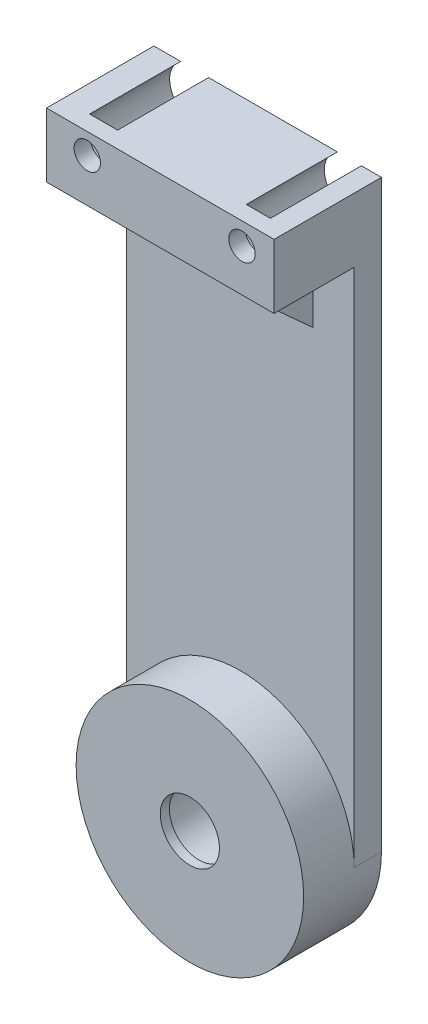
SolidWorks part; units mm, degrees
ref_plane "Plano frontal" through (0, 0, 0) normal (0, 0, 1) x (1, 0, 0)
ref_plane "Plano superior" through (0, 0, 0) normal (0, 1, 0) x (1, 0, 0)
ref_plane "Plano direito" through (0, 0, 0) normal (1, 0, 0) x (0, 0, -1)
sketch "Esboço2" plane through (0, 0, 0) normal (0, 0, 1) x (1, 0, 0)
  circle A0 centre (-0.4749, -0.0634) radius 12.5
  arc A1 (12.0247, -0.1594) -> (-12.9746, 0.0325) centre (-0.4749, -0.0634) ccw construction
extrude "Ressalto-extrusão1" add sketch "Esboço2" against normal offset from surface (5.55 mm away) 2 offset beyond the face yes
sketch "Esboço4" plane through (0, 0, -5.55) normal (0, 0, -1) x (-1, 0, 0)
  line L0 (-12.0251, -0.0634) -> (-12.0251, 64.1202)
  line L1 (12.9749, -0.0634) -> (12.9749, 64.1202)
  line L2 (12.9749, 64.1202) -> (-12.0251, 64.1202)
  arc A0 (-12.0251, -0.0634) -> (12.9749, -0.0634) centre (0.4749, -0.0634) ccw
  circle A4 centre (0.4749, -0.0634) radius 12.5 construction
  dimension "D1" = 0.5
extrude "Ressalto-extrusão3" add sketch "Esboço4" along normal blind 3
sketch "Esboço5" plane through (0, 0, -8.55) normal (0, 0, -1) x (-1, 0, 0)
  line L0 (12.9749, -0.0634) -> (12.9749, 64.1202) construction
  line L1 (-12.0251, 64.1202) -> (12.9749, 64.1202)
  line L2 (-12.0251, 64.1202) -> (-12.0251, 57.0691)
  line L3 (-12.0251, 57.0691) -> (12.9749, 57.0691)
  line L5 (12.9749, 57.0691) -> (12.9749, 64.1202)
extrude "Ressalto-extrusão4" add sketch "Esboço5" against normal up to surface (11.8 mm away)
hole_wizard "Rebaixo para SHCS M2.51" positions "Esboço6" profile "Esboço7" counterbore size "M2.5" standard "Ansi Metric" end condition up to next
sketch "Esboço6" plane through (0, 0, -8.55) normal (0, 0, -1) x (-1, 0, 0)
  circle A0 centre (-8.4995, 61.7078) radius 1.35 construction
  circle A1 centre (8.5, 61.8383) radius 1.35 construction
  point P0 (-8.4995, 61.7078)
  point P2 (8.5, 61.8383)
sketch "Esboço7" plane through (8.4995, 61.7078, -8.55) normal (1, 0, 0) x (0, 1, 0)
  line L0 (0, 0) -> (0, 11.8)
  line L1 (0, 11.8) -> (1.45, 11.8)
  line L3 (1.45, 11.8) -> (1.45, 10)
  line L4 (1.45, 10) -> (2.75, 10)
  line L5 (2.75, 10) -> (2.75, 0)
  line L7 (2.75, 0) -> (0, 0)
  line L11 (0, -6.35) -> (0, 107.95) construction
  dimension "Thru Hole Dia." = 2.9
  dimension "Thru Hole Depth" = 11.8
  dimension "C'Bore Dia." = 5.5
  dimension "C'Bore Depth" = 10
sketch "Esboço10" plane through (0, 0, 0) normal (1, 0, 0) x (0, 0, -1)
  line L0 (-3.25, 57.0691) -> (5.55, 49.0691)
  line L1 (5.55, -0.0634) -> (5.55, 57.0691) construction
  line L2 (-3.25, 57.0691) -> (5.55, 57.0691) construction
  dimension "D1" = 8
rib "Nervura1" sketch "Esboço10" sketch "Esboço10" thickness 15 extrusion direction parallel to sketch draft on no parameters "D1"=15
sketch "Esboço11" plane through (0, 0, -5.55) normal (0, 0, 1) x (1, 0, 0)
  line L0 (7.5, 49.0691) -> (-7.5, 49.0691) construction
  line L1 (4.5, 49.0691) -> (-4.5, 49.0691)
  line L2 (4.5, 49.0691) -> (4.5, 57.0691)
  line L3 (4.5, 57.0691) -> (-4.5, 57.0691)
  line L4 (-4.5, 49.0691) -> (-4.5, 57.0691)
  line L5 (7.5, 57.0691) -> (-7.5, 57.0691) construction
  line L6 (7.5, 57.0691) -> (7.5, 49.0691) construction
  point P8 (0, 57.0691)
  point P9 (0, 57.0691)
  dimension "D1" = 3
extrude "Corte-extrusão1" cut sketch "Esboço11" along normal up to next
sketch "Esboço12" plane through (0, 0, -8.55) normal (0, 0, -1) x (-1, 0, 0)
  circle A0 centre (0.4749, -0.0634) radius 3.25 construction
  circle A1 centre (0.4749, -0.0634) radius 3.25
extrude "Corte-extrusão2" cut sketch "Esboço12" against normal through all
sketch "Esboço13" plane through (0, 0, -8.55) normal (0, 0, -1) x (-1, 0, 0)
  circle A0 centre (0.4749, -0.0634) radius 4 construction
  circle A1 centre (0.4749, -0.0634) radius 4
extrude "Corte-extrusão3" cut sketch "Esboço13" against normal offset from surface (7.55 mm away) 1 up to face at (2.7751, -0.0634, 0)
